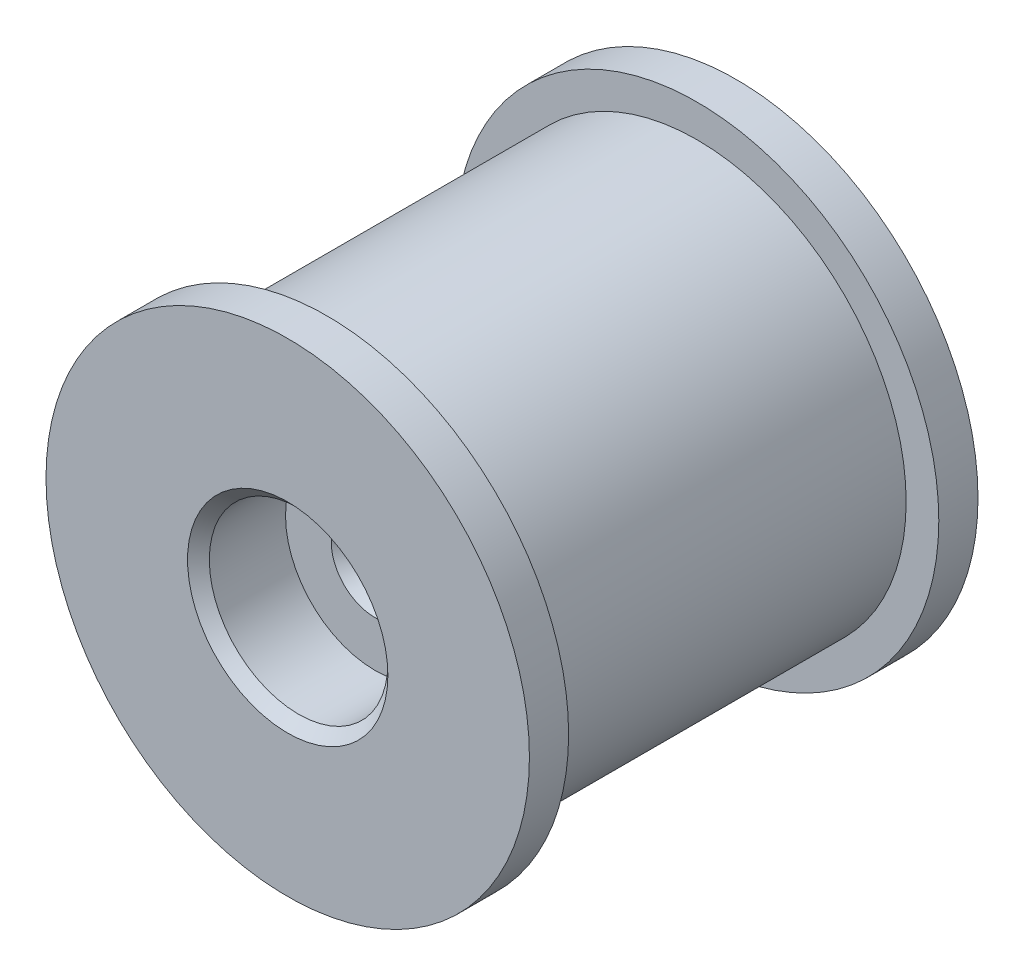
SolidWorks part; units mm, degrees
ref_plane "Ebene vorne" through (0, 0, 0) normal (0, 0, 1) x (1, 0, 0)
ref_plane "Ebene oben" through (0, 0, 0) normal (0, 1, 0) x (1, 0, 0)
ref_plane "Ebene rechts" through (0, 0, 0) normal (1, 0, 0) x (0, 0, -1)
sketch "Skizze1" plane through (0, 0, 0) normal (0, 0, 1) x (1, 0, 0)
  circle A0 centre (0, 0) radius 9.6
  dimension "D1" = 19.2
extrude "Aufsatz-Linear austragen1" add sketch "Skizze1" along normal blind 10.3 and the other way blind 10.3
ref_axis "Rotationsachse" [suppressed] through (0, 0, -9.8) along (0, 0, 1)
sketch "Skizze2" plane through (0, 0, 10.3) normal (0, 0, 1) x (1, 0, 0)
  circle A0 centre (0, 0) radius 11.1
  dimension "D1" = 22.2
extrude "Aufsatz-Linear austragen2" add sketch "Skizze2" against normal blind 1.8
sketch "Skizze3" plane through (0, 0, -10.3) normal (0, 0, -1) x (-1, 0, 0)
  circle A0 centre (0, 0) radius 11.1
  dimension "D1" = 22.2
extrude "Aufsatz-Linear austragen3" add sketch "Skizze3" against normal blind 1.8
sketch "Skizze8" plane through (0, 0, 0) normal (1, 0, 0) x (0, 0, -1)
  line L0 (10.3, 0) -> (10.3, 8)
  line L1 (10.3, -11.1) -> (10.3, 11.1) construction
  line L2 (10.3, 8) -> (8.5, 8)
  line L3 (8.5, 11.1) -> (8.5, -11.1) construction
  line L8 (8.5, 8) -> (-2.7, 6)
  line L9 (-2.7, 6) -> (-2.7, 1.5)
  line L10 (-2.7, 1.5) -> (-6.3, 1.5)
  line L11 (-6.3, 1.5) -> (-6.3, 4.1)
  line L12 (-6.3, 4.1) -> (-10.3, 4.1)
  line L13 (-10.3, 11.1) -> (-10.3, -11.1) construction
  line L14 (-10.3, 4.1) -> (-10.3, 0)
  line L15 (-10.3, 0) -> (10.3, 0)
  dimension "D1" = 8
  dimension "D2" = 4
  dimension "D3" = 4.1
  dimension "D4" = 13
  dimension "D5" = 6
  dimension "D6" = 1.5
revolve "Schnitt-Rotation1" cut sketch "Skizze8" angle 360 about axis through (0, 0, -9.8) along (0, 0, 1)
chamfer "Fase1" distance 0.5 3 edges at (-1.5, 0, 6.3) (-1.5, 0, 2.7) (-4.1, 0, 10.3)
